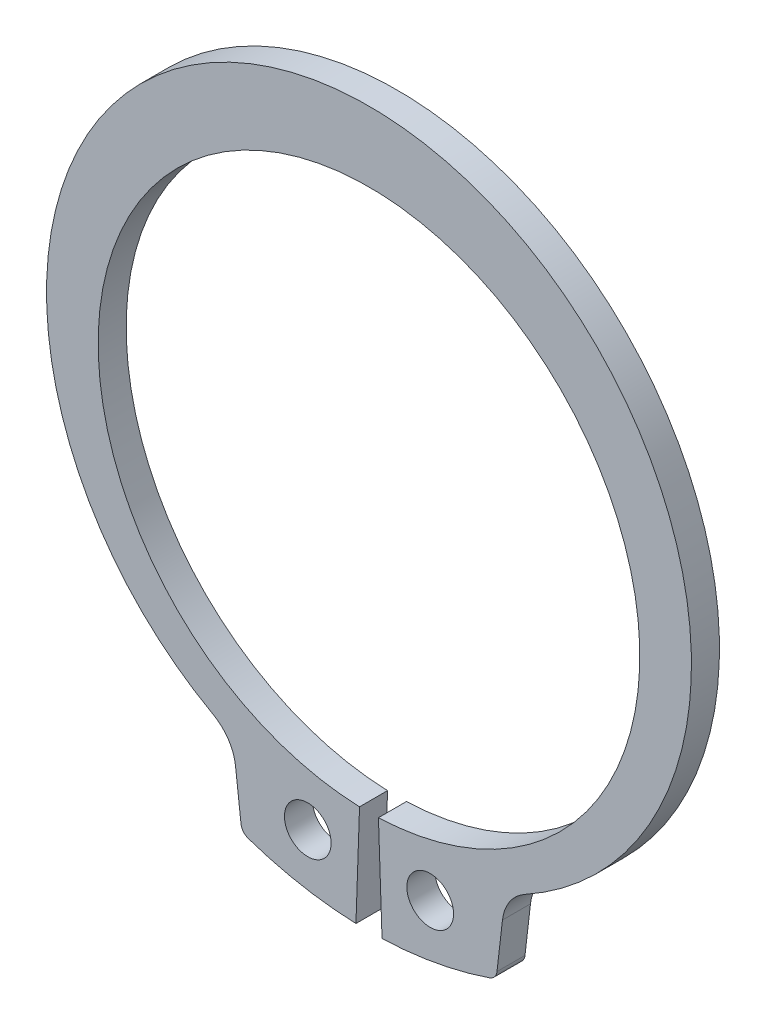
SolidWorks part; units mm, degrees
ref_plane "Front" through (0, 0, 0) normal (0, 0, 1) x (1, 0, 0)
ref_plane "Top" through (0, 0, 0) normal (0, 1, 0) x (1, 0, 0)
ref_plane "Right" through (0, 0, 0) normal (1, 0, 0) x (0, 0, -1)
sketch "Sketch1" plane through (0, 0, 0) normal (0, 0, 1) x (1, 0, 0)
  line L0 (0, 0) -> (-10.0459, -5.8) construction
  line L1 (0, 16) -> (0, -16) construction
  line L2 (-5.4478, -15.0543) -> (-5.8318, -11.7303) construction
  line L4 (-5.8318, -11.7303) -> (-6.4996, -13.0735) construction
  line L5 (-5.8318, -11.7303) -> (0, 0) construction
  line L6 (0, 11.6) -> (0, 14.6) construction
  line L7 (0, 14.6) -> (0, 13.1) construction
  line L8 (0, -11.6) -> (0, -16) construction
  line L9 (-3.0403, -15.7184) -> (0, 0) construction
  line L10 (0, 0) -> (-0.5587, -16) construction
  line L11 (-5.4478, -15.0543) -> (0, 0) construction
  line L12 (-5.7233, -12.6699) -> (-6.6751, -11.3018) construction
  line L13 (-6.1992, -11.9859) -> (-5.8318, -11.7303) construction
  line L14 (-2.2029, -11.3889) -> (-3.0403, -15.7184) construction
  line L15 (-2.6216, -13.5537) -> (-1.6398, -13.7436) construction
  arc A0 (0, 14.6) -> (-5.8318, -11.7303) centre (0, 0.789) ccw construction
  circle A2 centre (0, 0) radius 14.6 construction
  arc A3 (-5.4478, -15.0543) -> (-0.5587, -16) centre (0, 0) ccw construction
  circle A4 centre (0, 0) radius 11.6 construction
  circle A6 centre (-2.6216, -13.5537) radius 1 construction
  arc A7 (-6.6751, -11.3018) -> (-5.7233, -12.6699) centre (-7.5849, -12.9499) cw construction
  circle A9 centre (0, 0) radius 12.5 construction
  circle A10 centre (0, 0) radius 11.95 construction
  point P5 (-10.0459, -5.8)
  point P24 (-4.9681, -13.7287)
  point P35 (0, 14.6)
  point P36 (0, 11.6)
  point P37 (0, -11.6)
  point P38 (0, -16)
  dimension "Hole Diameter" = 2
  dimension "D10" = 1.8826
  dimension "For OD" = 25
  dimension "ID" = 23.2
  dimension "Max Sec." = 3
  dimension "Lug Height" = 4.4
  dimension "D6" = 2
  dimension "D5" = 3.3462
  dimension "D8" = 1.6667
  dimension "D3" = 120
  dimension "D2" = 5
  dimension "D4" = 1.6667
sketch "Sketch2" plane through (0, 0, 0) normal (-1, 0, 0) x (0, 1, 0)
  line L0 (-14.6, 0.6) -> (-14.6, -0.6) construction
  line L1 (14.6, -0.65) -> (14.6, 0.65) construction
  line L2 (0, 0.6) -> (0, -0.6) construction
  line L4 (-14.6, 0) -> (14.6, 0) construction
  point P3 (-14.6, 0)
  point P6 (0, 0)
  point P14 (14.6, 0)
  dimension "Thickness" = 1.2
  dimension "For Groove Width" = 1.3
sketch "Sketch4" plane through (0, 0, 0) normal (0, 0, 1) x (1, 0, 0)
  line L0 (-5.4478, -15.0543) -> (-5.8318, -11.7303) construction
  line L1 (-5.4478, -15.0543) -> (-5.8318, -11.7303)
  line L2 (0, 14.6) -> (0, 11.6)
  line L3 (-0.5587, -16) -> (-0.4048, -11.5929)
  line L4 (0, 0) -> (-0.5587, -16) construction
  arc A0 (0, 14.6) -> (-5.8318, -11.7303) centre (0, 0.789) ccw construction
  arc A1 (-5.4478, -15.0543) -> (-0.5587, -16) centre (0, 0) ccw construction
  circle A2 centre (-2.6216, -13.5537) radius 1 construction
  arc A4 (0, 14.6) -> (-5.8318, -11.7303) centre (0, 0.789) ccw
  arc A5 (-5.4478, -15.0543) -> (-0.5587, -16) centre (0, 0) ccw
  circle A6 centre (-2.6216, -13.5537) radius 1
  circle A7 centre (0, 0) radius 11.6 construction
  arc A8 (0, 11.6) -> (-0.4048, -11.5929) centre (0, 0) ccw
extrude "Boss-Extrude1" add sketch "Sketch4" along normal mid plane 1.2
fillet "Fillet1" radius 1.8826 1 edges at (-5.8318, -11.7303, 0)
fillet "Fillet2" radius 0.4707 1 edges at (-5.4478, -15.0543, 0)
mirror "Mirror1" about plane through (0, 14.6, 0.6) normal (-1, 0, 0) of bodies 109
sketch "Sketch3" plane through (0, 0, 0.6) normal (0, 0, 1) x (1, 0, 0)
  line L0 (5.9382, -9.9648) -> (6.6761, -11.3012) construction
  line L1 (6.6761, -11.3012) -> (8.0124, -10.5633) construction
  line L2 (0, 14.6) -> (0, 11.6) construction
  circle A0 centre (0, 0) radius 11.6 construction
  arc A1 (6.6761, -11.3012) -> (-6.6761, -11.3012) centre (0, 0.789) ccw construction
ref_axis "Axis1" through (0, 0, -0.66) along (0, 0, 1)
ref_plane "Plane1" through (0, 0, 0) normal (0, 0, -1) x (-1, 0, 0)
equation "\"D1@Fillet1\" = \"D10@Sketch1\""
equation "\"D1@Fillet2\" = \"D10@Sketch1\" / 4"
equation "\"Thickness@Boss-Extrude1\"  = \"Ring Thickness@Sketch5\""
equation "\"D2@Sketch1\"=\"Hole Diameter@Sketch1\"*2.5"
equation "\"D4@Sketch1\"=\"D2@Sketch1\"/3"
equation "\"D8@Sketch1\"=\"D4@Sketch1\""
